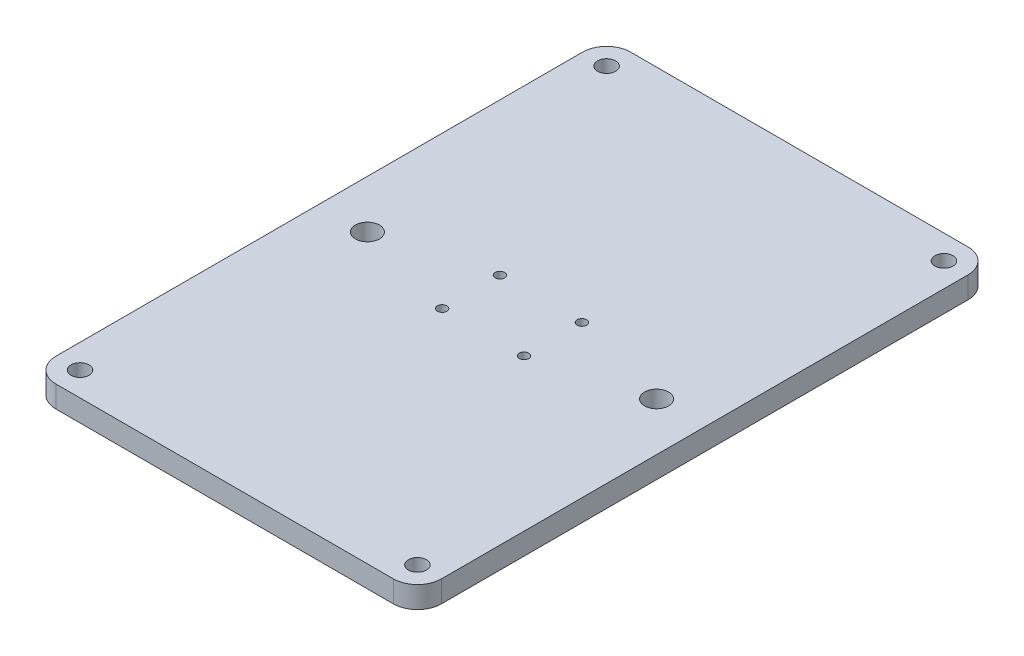
SolidWorks part; units mm, degrees
ref_plane "Front Plane" through (0, 0, 0) normal (0, 0, 1) x (1, 0, 0)
ref_plane "Top Plane" through (0, 0, 0) normal (0, 1, 0) x (1, 0, 0)
ref_plane "Right Plane" through (0, 0, 0) normal (1, 0, 0) x (0, 0, -1)
sketch "Sketch1" plane through (0, 12.5, 0) normal (0, 1, 0) x (1, 0, 0)
  line L1 (-44.45, -75.7199) -> (44.45, -75.7199)
  line L2 (-50.8, -69.3699) -> (-50.8, 69.3699)
  line L3 (-44.45, 75.7199) -> (44.45, 75.7199)
  line L4 (50.8, -69.3699) -> (50.8, 69.3699)
  line L5 (-50.8, -75.7199) -> (50.8, 75.7199) construction
  line L6 (-50.8, 75.7199) -> (50.8, -75.7199) construction
  line L7 (-12.5, -75.7199) -> (0, -75.7199) construction
  line L8 (-38.1, 0) -> (38.1, 0) construction
  line L10 (-44.45, -69.3699) -> (44.45, -69.3699) construction
  line L11 (-44.45, -69.3699) -> (-44.45, 69.3699) construction
  line L12 (-44.45, 69.3699) -> (44.45, 69.3699) construction
  line L13 (44.45, -69.3699) -> (44.45, 69.3699) construction
  line L14 (-44.45, -69.3699) -> (44.45, 69.3699) construction
  line L15 (-44.45, 69.3699) -> (44.45, -69.3699) construction
  arc A0 (44.45, -75.7199) -> (50.8, -69.3699) centre (44.45, -69.3699) ccw
  arc A1 (-44.45, -75.7199) -> (-50.8, -69.3699) centre (-44.45, -69.3699) cw
  arc A2 (-50.8, 69.3699) -> (-44.45, 75.7199) centre (-44.45, 69.3699) cw
  arc A3 (44.45, 75.7199) -> (50.8, 69.3699) centre (44.45, 69.3699) cw
  circle A4 centre (-10.795, 7.62) radius 1.25 construction
  circle A5 centre (-10.795, -7.62) radius 1.25 construction
  circle A6 centre (10.795, -7.62) radius 1.25 construction
  circle A7 centre (10.795, 7.62) radius 1.25 construction
  circle A8 centre (-10.795, 7.62) radius 1.25
  circle A9 centre (-10.795, -7.62) radius 1.25
  circle A10 centre (10.795, -7.62) radius 1.25
  circle A11 centre (10.795, 7.62) radius 1.25
  circle A13 centre (38.1, 0) radius 3.175
  circle A15 centre (-38.1, 0) radius 3.175
  circle A16 centre (44.45, 69.3699) radius 2.3812
  circle A17 centre (-44.45, 69.3699) radius 2.3812
  circle A18 centre (-44.45, -69.3699) radius 2.3812
  circle A19 centre (44.45, -69.3699) radius 2.3812
  point P0 (0, 0)
  point P32 (0, 0)
  point P45 (31.9269, 0)
  point P47 (44.45, 63.7101)
  point P48 (44.45, 49.4203)
  point P49 (44.45, 55.9486)
  dimension "D2" = 6.35
  dimension "D4" = 6.35
  dimension "D5" = 4.7625
  dimension "D1" = 101.6
  dimension "D3" = 6.35
  dimension "D6" = 76.2
extrude "Boss-Extrude1" add sketch "Sketch1" along normal blind 5.715
